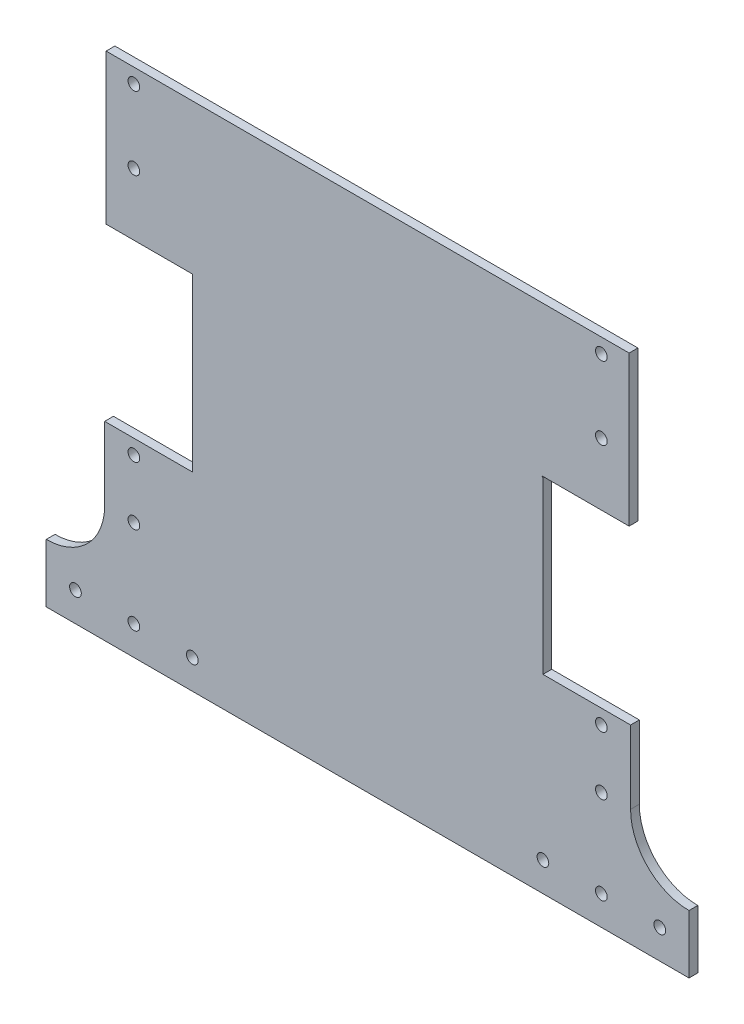
SolidWorks part; units mm, degrees
material "雪松树"
ref_plane "前视基准面" through (0, 0, 0) normal (0, 0, 1) x (1, 0, 0)
ref_plane "上视基准面" through (0, 0, 0) normal (0, 1, 0) x (1, 0, 0)
ref_plane "右视基准面" through (0, 0, 0) normal (1, 0, 0) x (0, 0, -1)
other "Configuration Table"
sketch "草图1" plane through (0, 0, 0) normal (0, 0, 1) x (1, 0, 0)
  line L0 (90, 207.6147) -> (90, -56.1906) construction
  line L1 (0, 0) -> (180, 0)
  line L2 (0, 0) -> (0, 150)
  line L4 (180, 0) -> (180, 150)
  line L13 (0, 65) -> (30, 65)
  line L14 (180, 123.1806) -> (150, 123.1806)
  line L15 (180, 123.1806) -> (180, 65)
  line L16 (180, 65) -> (150, 65)
  line L17 (150, 123.1806) -> (150, 65)
  line L18 (30, 123.1806) -> (30, 65)
  line L19 (0, 123.1806) -> (30, 123.1806)
  line L20 (0, 123.1806) -> (0, 65)
  line L21 (180, 20) -> (200, 20)
  line L22 (0, 0) -> (-20, 0)
  line L23 (0, 0) -> (0, 20)
  line L24 (0, 20) -> (-20, 20)
  line L25 (-20, 0) -> (-20, 20)
  line L26 (200, 0) -> (200, 20)
  line L27 (180, 0) -> (200, 0)
  line L28 (180, 0) -> (180, 20)
  line L29 (0, 150) -> (0, 175)
  line L30 (0, 175) -> (180, 175)
  line L31 (180, 175) -> (180, 150)
  line L32 (200, 0) -> (180, 0)
  line L33 (180, 20) -> (180, 65)
  dimension "D1" = 150
  dimension "D2" = 180
  dimension "D3" = 90
  dimension "D5" = 30
  dimension "D7" = 20
  dimension "D8" = 20
  dimension "D9" = 25
extrude "凸台-拉伸1" add sketch "草图1" along normal blind 3
fillet "圆角2" radius 20 6 edges at (0, 20, 1.5) (180, 20, 1.5) (-10, 20, 3) (-10, 20, 0) (190, 20, 3) (190, 20, 0)
sketch "草图2" plane through (0, 0, 3) normal (0, 0, 1) x (1, 0, 0)
  line L0 (90, 182.8416) -> (90, -50.9319) construction
  line L1 (170, 68) -> (170, -4.4257) construction
  line L3 (170, 190.2129) -> (170, 72) construction
  line L4 (180, 40) -> (180, 65) construction
  line L5 (-20, 0) -> (200, 0) construction
  line L6 (170, 10) -> (190, 10) construction
  line L7 (170, 10) -> (170, 40) construction
  line L8 (10, 10) -> (10, 40) construction
  line L9 (10, 10) -> (-10, 10) construction
  circle A0 centre (170, 10) radius 2
  circle A1 centre (190, 10) radius 2
  circle A4 centre (170, 40) radius 2
  circle A6 centre (190, 40) radius 2 [skipped]
  circle A7 centre (190, 70) radius 2 [skipped]
  circle A8 centre (150, 10) radius 2
  circle A9 centre (30, 10) radius 2
  circle A11 centre (10, 40) radius 2
  circle A12 centre (-10, 10) radius 2
  circle A13 centre (10, 10) radius 2
  circle A14 centre (170, 145) radius 2
  circle A15 centre (10, 145) radius 2
  arc A16 (170, 72) -> (170, 68) centre (170, 70) ccw [skipped]
  circle A17 centre (170, 60) radius 2
  circle A18 centre (10, 60) radius 2
  circle A19 centre (170, 170) radius 2
  circle A20 centre (10, 170) radius 2
  dimension "D3" = 4
  dimension "D4" = 10
  dimension "D9" = 10
  dimension "D10" = 4
  dimension "D11" = 20
  dimension "D12" = 10
  dimension "D13" = 4
  dimension "D14" = 4
  dimension "D15" = 4
  dimension "D16" = 20
  dimension "D2" = 10
  dimension "D7" = 20
  dimension "D8" = 30
  dimension "D17" = 25
  dimension "D5" = 2
  dimension "D6" = 3
extrude "切除-拉伸1" cut sketch "草图2" against normal blind 3
sketch "草图4" plane through (0, 0, 3) normal (0, 0, 1) x (1, 0, 0)
  line L0 (0.5, 175) -> (0.5, 123.6806)
  line L1 (0, 175) -> (180, 175) construction
  line L2 (0.5, 123.6806) -> (30.0553, 123.6806)
  line L3 (30.0553, 123.6806) -> (30, 123.1806)
  line L4 (30, 123.1806) -> (-10.6984, 117.1878)
  line L5 (-10.6984, 117.1878) -> (-9.2727, 179.4438)
  line L6 (-9.2727, 179.4438) -> (-1.5739, 179.4438)
  line L9 (-1.5739, 179.4438) -> (0.5, 175)
  line L10 (179.5, 175) -> (179.5, 123.6806)
  line L11 (179.5, 123.6806) -> (149.725, 123.6806)
  line L12 (149.725, 123.6806) -> (150, 123.1806)
  line L13 (150, 123.1806) -> (194.1894, 109.3029)
  line L14 (194.1894, 109.3029) -> (194.4297, 189.3064)
  line L15 (194.4297, 189.3064) -> (181.7007, 189.3064)
  line L16 (181.7007, 189.3064) -> (179.5, 175)
  line L17 (0, 123.1806) -> (0, 175) construction
  line L18 (0, 123.1806) -> (30, 123.1806) construction
  line L19 (180, 123.1806) -> (150, 123.1806) construction
  line L20 (180, 123.1806) -> (180, 175) construction
  dimension "D1" = 0.5
  dimension "D2" = 0.5
  dimension "D3" = 0.5
  dimension "D4" = 0.5
extrude "切除-拉伸2" cut sketch "草图4" against normal blind 10
